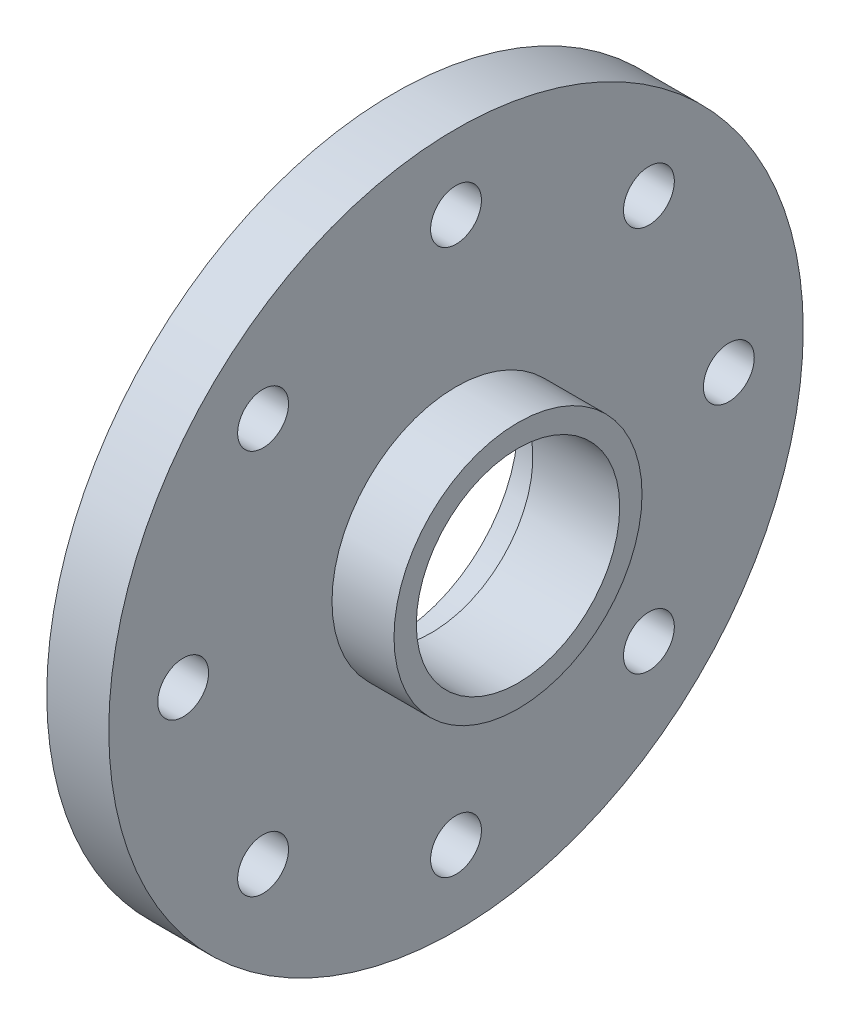
SolidWorks part; units mm, degrees
material "2024 Alloy (SN)"
ref_plane "Front Plane" through (0, 0, 0) normal (0, 0, 1) x (1, 0, 0)
ref_plane "Top Plane" through (0, 0, 0) normal (0, 1, 0) x (1, 0, 0)
ref_plane "Right Plane" through (0, 0, 0) normal (1, 0, 0) x (0, 0, -1)
sketch "Sketch1" plane through (0, 0, 0) normal (1, 0, 0) x (0, 0, -1)
  circle A0 centre (0, 0) radius 4.1
  circle A1 centre (0, 0) radius 14
  dimension "D1" = 8.2
  dimension "D2" = 28
extrude "Boss-Extrude1" add sketch "Sketch1" along normal blind 2.5
sketch "Sketch2" plane through (2.5, 0, 0) normal (1, 0, 0) x (0, 0, -1)
  circle A0 centre (0, 0) radius 4.1
  circle A1 centre (0, 0) radius 5
  circle A2 centre (0, 0) radius 4.1 construction
  dimension "D1" = 10
extrude "Boss-Extrude2" add sketch "Sketch2" along normal blind 2.5
hole_wizard "M2.5x0.45 Tapped Hole1" positions "Sketch6" profile "Sketch5" tap size "M2.5x0.45" standard "ANSI Metric" end condition through all
sketch "Sketch6" plane through (5, 0, 0) normal (1, 0, 0) x (0, 0, -1)
  point P25 (0, 11)
  point P36 (7.7782, 7.7782)
  point P37 (11, 0)
  point P38 (7.7782, -7.7782)
  point P39 (0, -11)
  point P40 (-7.7782, -7.7782)
  point P41 (-11, 0)
  point P42 (-7.7782, 7.7782)
  point P43 (0, 0)
  dimension "D1" = 11
  dimension "D2" = 8
cosmetic thread "Hole Thread1" parameters "D2"=2.5
cosmetic thread "Hole Thread2" parameters "D2"=2.5
cosmetic thread "Hole Thread3" parameters "D2"=2.5
cosmetic thread "Hole Thread4" parameters "D2"=2.5
cosmetic thread "Hole Thread5" parameters "D2"=2.5
cosmetic thread "Hole Thread6" parameters "D2"=2.5
cosmetic thread "Hole Thread7" parameters "D2"=2.5
cosmetic thread "Hole Thread8" parameters "D2"=2.5
sketch "Sketch5" plane through (5, 11, 0) normal (0, 1, 0) x (0, 0, -1)
  line L0 (0, 0) -> (0, 5)
  line L1 (0, 5) -> (1.025, 5)
  line L2 (1.025, 5) -> (1.025, 0)
  line L5 (1.025, 0) -> (0, 0)
  line L11 (0, -6.35) -> (0, 107.95) construction
  dimension "Thru Tap Drill Dia." = 2.05
  dimension "Thru Tap Drill Depth" = 5
sketch "Sketch7" plane through (0, 0, 0) normal (-1, 0, 0) x (0, 0, 1)
  circle A0 centre (0, 0) radius 5
  dimension "D1" = 10
extrude "Cut-Extrude1" cut sketch "Sketch7" against normal blind 1.5
